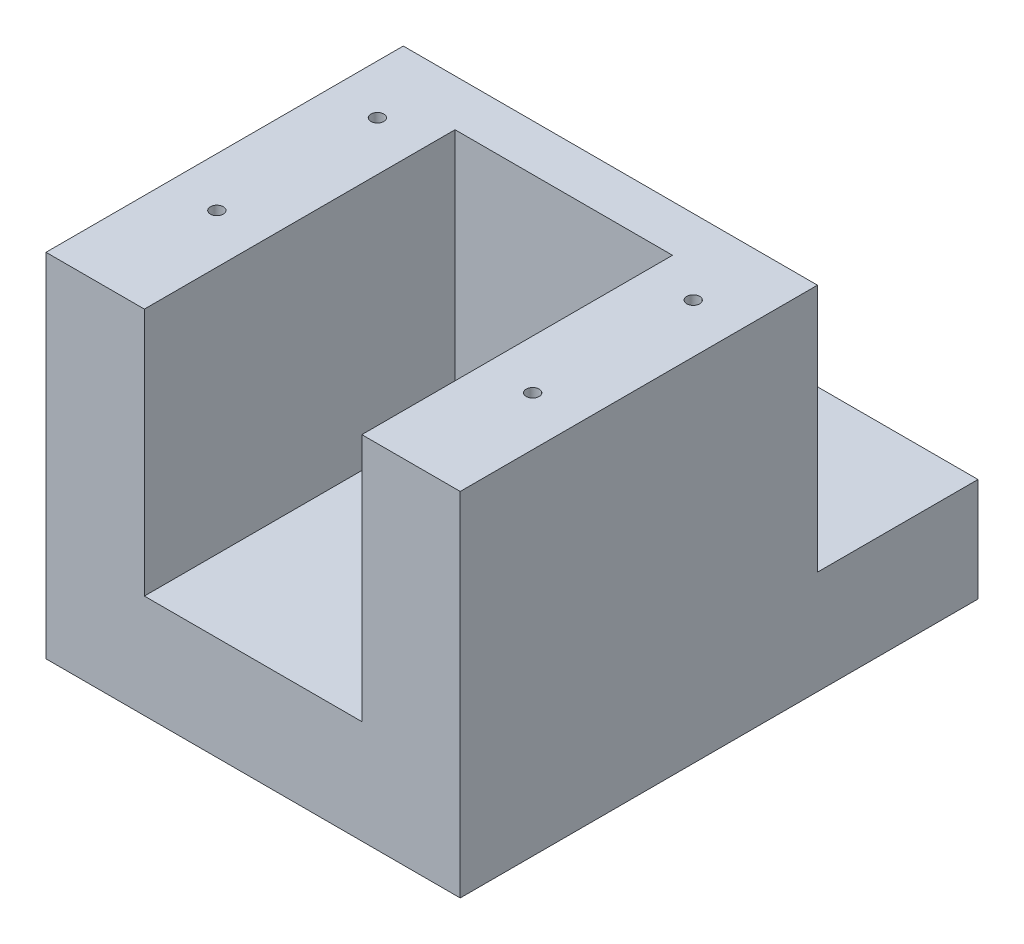
SolidWorks part; units mm, degrees
ref_plane "Front Plane" through (0, 0, 0) normal (0, 0, 1) x (1, 0, 0)
ref_plane "Top Plane" through (0, 0, 0) normal (0, 1, 0) x (1, 0, 0)
ref_plane "Right Plane" through (0, 0, 0) normal (1, 0, 0) x (0, 0, -1)
sketch "Sketch2" plane through (0, -39.8991, 0) normal (0, 1, 0) x (1, 0, 0)
  line L0 (-296.943, -352.1262) -> (-296.943, -252.1262) construction
  line L5 (-336.943, -252.1262) -> (-256.943, -252.1262)
  line L6 (-336.943, -252.1262) -> (-336.943, -352.1262)
  line L11 (-336.943, -352.1262) -> (-256.943, -352.1262)
  line L12 (-256.943, -252.1262) -> (-256.943, -352.1262)
  line L13 (-296.943, -272.1262) -> (-336.943, -272.1262) construction
  point P0 (-296.943, -272.1262)
  point P8 (-296.943, -272.1262)
  point P10 (-336.943, -252.1262)
  point P11 (-310.291, -331.3603)
  point P12 (-256.943, -352.1262)
  dimension "D1" = 40
  dimension "D2" = 80
  dimension "D3" = 20
  dimension "D4" = 100
extrude "Boss-Extrude1" add sketch "Sketch2" along normal blind 10
sketch "Sketch4" plane through (0, -29.8991, 0) normal (0, 1, 0) x (1, 0, 0)
  line L0 (-296.943, -352.1262) -> (-296.943, -271.3603) construction
  line L1 (-336.943, -252.1262) -> (-303.943, -252.1262)
  line L2 (-336.943, -252.1262) -> (-336.943, -352.1262)
  line L3 (-336.943, -352.1262) -> (-256.943, -352.1262)
  line L4 (-256.943, -252.1262) -> (-256.943, -352.1262)
  line L5 (-289.943, -252.1262) -> (-256.943, -252.1262)
  line L7 (-303.943, -252.1262) -> (-303.943, -283.1262)
  line L8 (-303.943, -283.1262) -> (-289.943, -283.1262)
  line L9 (-289.943, -252.1262) -> (-289.943, -283.1262)
  point P12 (-296.943, -283.1262)
  dimension "D1" = 31
  dimension "D2" = 14
extrude "Boss-Extrude3" add sketch "Sketch4" along normal blind 10
sketch "Sketch5" plane through (0, -19.8991, 0) normal (0, 1, 0) x (1, 0, 0)
  line L0 (-256.943, -352.1262) -> (-256.943, -252.1262) construction
  line L1 (-336.943, -352.1262) -> (-256.943, -352.1262)
  line L2 (-336.943, -352.1262) -> (-336.943, -283.1262)
  line L3 (-336.943, -283.1262) -> (-256.943, -283.1262)
  line L4 (-256.943, -352.1262) -> (-256.943, -283.1262)
  line L5 (-289.943, -283.1262) -> (-303.943, -283.1262) construction
  line L7 (-317.943, -292.1262) -> (-275.943, -292.1262)
  line L8 (-317.943, -292.1262) -> (-317.943, -352.1262)
  line L9 (-317.943, -352.1262) -> (-275.943, -352.1262)
  line L10 (-275.943, -292.1262) -> (-275.943, -352.1262)
  point P13 (-296.943, -283.1262)
  point P14 (-296.943, -292.1262)
  line M4 (-336.943, -252.1262) -> (-336.943, -352.1262)
  line M5 (-336.943, -352.1262) -> (-256.943, -352.1262)
  line M6 (-256.943, -352.1262) -> (-256.943, -252.1262)
  line M9 (-289.943, -283.1262) -> (-303.943, -283.1262)
  dimension "D1" = 60
  dimension "D2" = 42
extrude "Boss-Extrude4" add sketch "Sketch5" along normal blind 48 contours L7 L10 L3 L8 M5 M6 M9 M4 region at (-335.8865, -19.8991, 317.6262)
sketch "Sketch8" plane through (0, 28.1009, 0) normal (0, 1, 0) x (1, 0, 0)
  line L0 (-336.943, -317.6262) -> (-317.943, -317.6262) construction
  line L1 (-336.943, -283.1262) -> (-336.943, -352.1262) construction
  line L2 (-317.943, -292.1262) -> (-317.943, -352.1262) construction
  line L3 (-275.943, -317.6262) -> (-256.943, -317.6262) construction
  line L4 (-275.943, -292.1262) -> (-275.943, -352.1262) construction
  line L5 (-256.943, -352.1262) -> (-256.943, -283.1262) construction
  line L7 (-317.943, -292.1262) -> (-275.943, -292.1262) construction
  point P0 (-327.443, -297.6262)
  point P1 (-327.443, -328.6262)
  point P2 (-266.443, -328.6262)
  point P3 (-266.443, -297.6262)
  point P13 (-327.443, -317.6262)
  point P19 (-266.443, -317.6262)
  dimension "D1" = 31
  dimension "D2" = 5.5
hole_wizard "Ø2.5 (2.5) Diameter Hole2" positions "Sketch10" profile "Sketch11" hole size "Ø2.5" standard "ANSI Metric"
sketch "Sketch10" plane through (0, 28.1009, 0) normal (0, 1, 0) x (1, 0, 0)
  point P0 (-327.443, -328.6262)
  point P3 (-327.443, -297.6262)
  point P6 (-266.443, -297.6262)
  point P9 (-266.443, -328.6262)
sketch "Sketch11" plane through (-327.443, 28.1009, 328.6262) normal (1, 0, 0) x (0, 0, 1)
  line L0 (0, 0) -> (0, 5.7511)
  line L1 (0, 5.7511) -> (1.25, 5)
  line L2 (1.25, 5) -> (1.25, 0)
  line L5 (1.25, 0) -> (0, 0)
  line L10 (0, 5.7511) -> (-1.25, 5) construction
  line L11 (0, -6.35) -> (0, 107.95) construction
  dimension "Hole Dia." = 2.5
  dimension "Hole Depth" = 5
  dimension "Drill Angle" = 118
